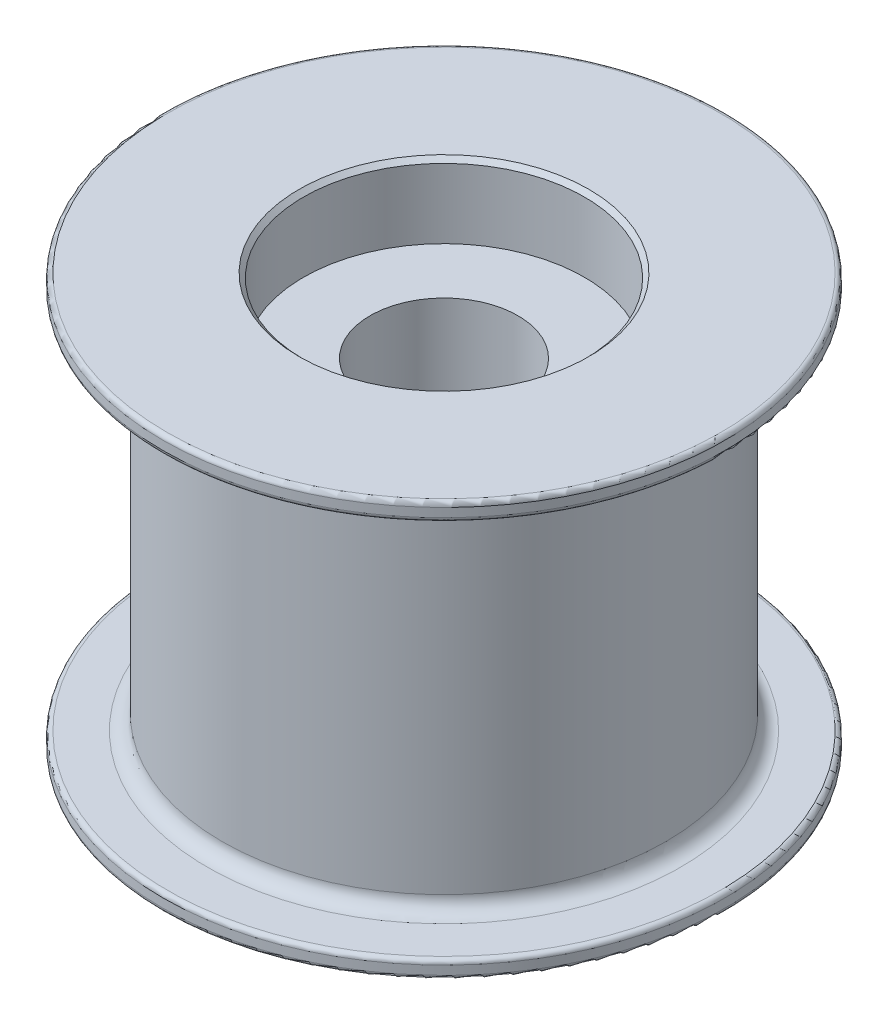
SolidWorks part; units mm, degrees
ref_plane "Front Plane" through (0, 0, 0) normal (0, 0, 1) x (1, 0, 0)
ref_plane "Top Plane" through (0, 0, 0) normal (0, 1, 0) x (1, 0, 0)
ref_plane "Right Plane" through (0, 0, 0) normal (1, 0, 0) x (0, 0, -1)
sketch "Sketch1" plane through (0, 0, 0) normal (0, 0, 1) x (1, 0, 0)
  line L0 (0, 11.9429) -> (0, 0) construction
  line L1 (-9.5, 14) -> (-19, 14)
  line L2 (-19, 14) -> (-19, 12.8)
  line L3 (-19, 12.8) -> (-15, 12.8)
  line L4 (-15, 12.8) -> (-15, 0)
  line L5 (-15, 0) -> (-5, 0)
  line L6 (-5, 0) -> (-5, 9)
  line L7 (-5, 9) -> (-9.5, 9)
  line L8 (-9.5, 9) -> (-9.5, 14)
  point P5 (0, 0)
  dimension "D1" = 1.2
  dimension "D2" = 14
  dimension "D3" = 5
  dimension "D4" = 5
  dimension "D5" = 9.5
  dimension "D6" = 4
  dimension "D7" = 19
revolve "Revolve1" add sketch "Sketch1" angle 360 about L0
fillet "Fillet1" radius 1 1 edges at (0, 12.8, 15)
chamfer "Chamfer1" distance 0.3 angle 45 1 edges at (0, 14, 9.5)
fillet "Fillet2" radius 0.3 2 edges at (0, 14, 19) (0, 12.8, 19)
mirror "Mirror1" about plane through (-15, 0, 0) normal (0, -1, 0) of bodies 101
ref_axis "Axis1" through (0, -11.8, 0) along (0, 1, 0)
